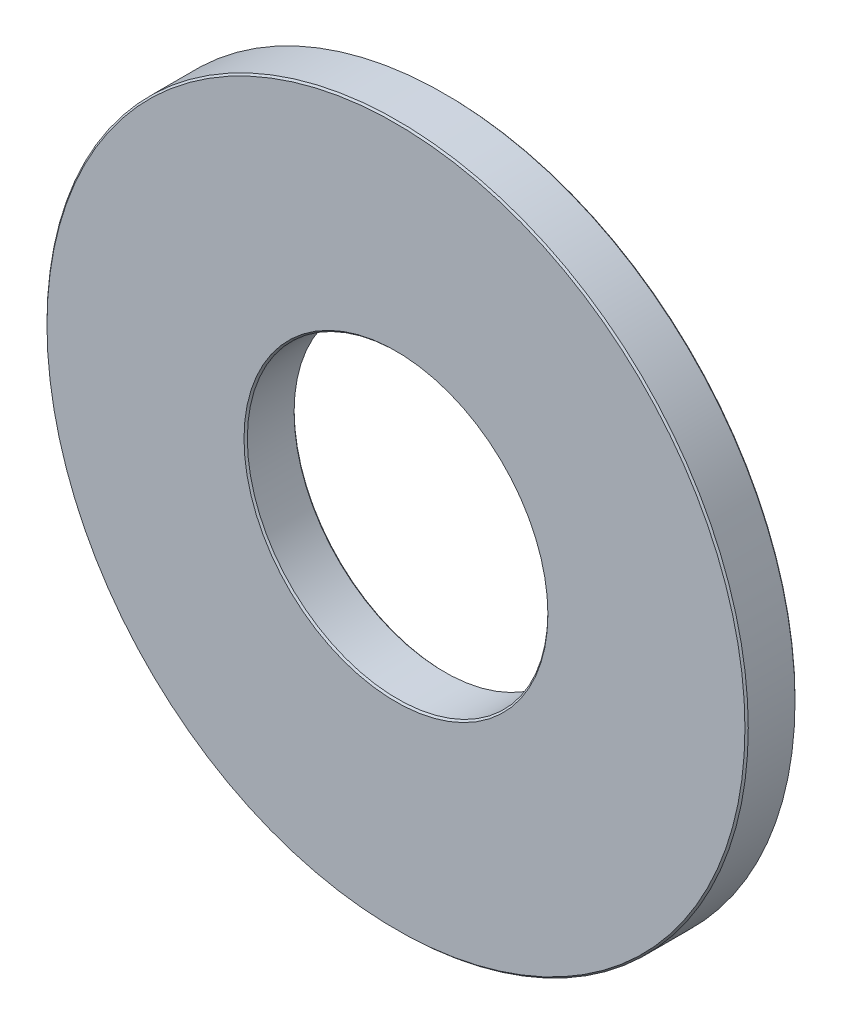
SolidWorks part; units mm, degrees
ref_plane "Front Plane" through (0, 0, 0) normal (0, 0, 1) x (1, 0, 0)
ref_plane "Top Plane" through (0, 0, 0) normal (0, 1, 0) x (1, 0, 0)
ref_plane "Right Plane" through (0, 0, 0) normal (1, 0, 0) x (0, 0, -1)
sketch "Sketch1" plane through (0, 0, 0) normal (0, 0, 1) x (1, 0, 0)
  circle A0 centre (0, 0) radius 2.25
  circle A1 centre (0, 0) radius 5.25
  dimension "D1" = 4.5
  dimension "D2" = 3
base flange "Base-Flange1" sketch "Sketch1" thickness 0.75 reverse thickness direction no parameters "D1"=0.75
chamfer "Chamfer1" distance 0.025 4 edges at (2.25, 0, 0) (2.25, 0, -0.75) (5.25, 0, 0) (5.25, 0, -0.75)
sketch "Bend-Lines1" [suppressed] plane through (0, 0, 0) normal (0, 1, 0) x (1, 0, 0)
sketch "Bounding-Box1" [suppressed] plane through (0, 0, 0) normal (0, 1, 0) x (1, 0, 0)
sheet metal parameters "Sheet-Metal1" thickness 0.75 parameters "D1"=0.75
flat pattern "Flat-Pattern1" [suppressed]
sketch "Bend-Lines2" plane through (0, 0, 0) normal (0, 1, 0) x (1, 0, 0)
sketch3d "Bounding-Box2" [suppressed]
  line L0 (-5.25, -5.25, 0) -> (5.25, -5.25, 0) construction
  line L1 (-5.25, 5.25, 0) -> (5.25, 5.25, 0) construction
  line L2 (-5.25, -5.25, 0) -> (-5.25, 5.25, 0) construction
  line L3 (5.25, -5.25, 0) -> (5.25, 5.25, 0) construction
